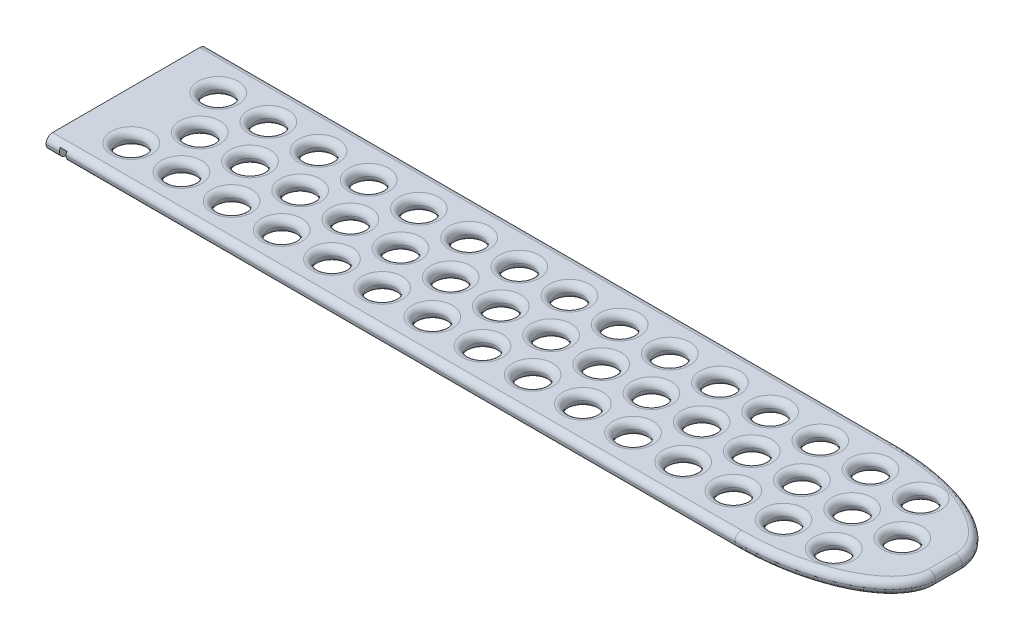
SolidWorks part; units mm, degrees
ref_plane "Front Plane" through (0, 0, 0) normal (0, 0, 1) x (1, 0, 0)
ref_plane "Top Plane" through (0, 0, 0) normal (0, 1, 0) x (1, 0, 0)
ref_plane "Right Plane" through (0, 0, 0) normal (1, 0, 0) x (0, 0, -1)
sketch "Sketch1" plane through (0, 0, 0) normal (0, 1, 0) x (1, 0, 0)
  line L1 (22.7264, 12) -> (146.7264, 12)
  line L2 (22.7264, 12) -> (22.7264, -12)
  line L3 (22.7264, -12) -> (146.7264, -12)
  line L4 (146.7264, 12) -> (146.7264, -12)
  dimension "D1" = 24
  dimension "D2" = 124
extrude "Boss-Extrude1" add sketch "Sketch1" along normal blind 2
fillet "Fillet1" radius 20 1 edges at (146.7264, 1, 12) second distance 10 first distance on face at (84.7264, 1, 12)
fillet "Fillet2" radius 20 1 edges at (146.7264, 1, -12) second distance 10 first distance on face at (84.7264, 1, -12)
sketch "Sketch4" plane through (0, 2, 0) normal (0, 1, 0) x (1, 0, 0)
  line L0 (30.9736, 6.5) -> (34.7264, 0) construction
  line L1 (34.7264, 0) -> (30.9736, -6.5) construction
  line L2 (22.7264, 12) -> (22.7264, -12) construction
  circle A0 centre (30.9736, 6.5) radius 2
  circle A1 centre (34.7264, 0) radius 2
  circle A2 centre (30.9736, -6.5) radius 2
  circle A3 centre (42.2292, 0) radius 2
  circle A4 centre (38.4764, 6.5) radius 2
  circle A5 centre (38.4764, -6.5) radius 2
  circle A6 centre (49.732, 0) radius 2
  circle A7 centre (45.9792, 6.5) radius 2
  circle A8 centre (45.9792, -6.5) radius 2
  circle A9 centre (57.2347, 0) radius 2
  circle A10 centre (53.482, 6.5) radius 2
  circle A11 centre (53.482, -6.5) radius 2
  circle A12 centre (64.7375, 0) radius 2
  circle A13 centre (60.9847, 6.5) radius 2
  circle A14 centre (60.9847, -6.5) radius 2
  circle A15 centre (72.2403, 0) radius 2
  circle A16 centre (68.4875, 6.5) radius 2
  circle A17 centre (68.4875, -6.5) radius 2
  circle A18 centre (79.7431, 0) radius 2
  circle A19 centre (75.9903, 6.5) radius 2
  circle A20 centre (75.9903, -6.5) radius 2
  circle A21 centre (87.2459, 0) radius 2
  circle A22 centre (83.4931, 6.5) radius 2
  circle A23 centre (83.4931, -6.5) radius 2
  circle A24 centre (94.7486, 0) radius 2
  circle A25 centre (90.9959, 6.5) radius 2
  circle A26 centre (90.9959, -6.5) radius 2
  circle A27 centre (102.2514, 0) radius 2
  circle A28 centre (98.4986, 6.5) radius 2
  circle A29 centre (98.4986, -6.5) radius 2
  circle A30 centre (109.7542, 0) radius 2
  circle A31 centre (106.0014, 6.5) radius 2
  circle A32 centre (106.0014, -6.5) radius 2
  circle A33 centre (117.257, 0) radius 2
  circle A34 centre (113.5042, 6.5) radius 2
  circle A35 centre (113.5042, -6.5) radius 2
  circle A36 centre (124.7597, 0) radius 2
  circle A37 centre (121.007, 6.5) radius 2
  circle A38 centre (121.007, -6.5) radius 2
  circle A39 centre (132.2625, 0) radius 2
  circle A40 centre (128.5097, 6.5) radius 2
  circle A41 centre (128.5097, -6.5) radius 2
  circle A42 centre (139.7653, 0) radius 2
  circle A43 centre (136.0125, 6.5) radius 2
  circle A44 centre (136.0125, -6.5) radius 2
  point P11 (22.7264, 0)
  dimension "D1" = 4
  dimension "D2" = 120
  dimension "D3" = 12
  dimension "D5" = 3.75
  dimension "D6" = 13
  dimension "D4" = 15
extrude "Cut-Extrude2" cut sketch "Sketch4" against normal through all
fillet "Fillet3" radius 1 102 edges at (30.9736, 0, -4.5) (113.5042, 0, 8.5) (117.257, 0, 2) (113.5042, 0, -4.5) (60.9847, 0, -4.5) (53.482, 0, 8.5) (57.2347, 0, 2) (53.482, 0, -4.5) (72.2403, 0, 2) (68.4875, 0, -4.5) (60.9847, 0, 8.5) (64.7375, 0, 2) (42.2292, 0, 2) (38.4764, 0, -4.5) (30.9736, 0, 8.5) (34.7264, 0, 2) (45.9792, 0, 8.5) (49.732, 0, 2) (45.9792, 0, -4.5) (38.4764, 0, 8.5) (102.2514, 0, 2) (98.4986, 0, -4.5) (90.9959, 0, 8.5) (94.7486, 0, 2) (106.0014, 0, 8.5) (109.7542, 0, 2) (106.0014, 0, -4.5) (98.4986, 0, 8.5) (75.9903, 0, 8.5) (79.7431, 0, 2) (75.9903, 0, -4.5) (68.4875, 0, 8.5) (90.9959, 0, -4.5) (83.4931, 0, 8.5) (87.2459, 0, 2) (83.4931, 0, -4.5) (30.9736, 2, -4.5) (113.5042, 2, 8.5) (117.257, 2, 2) (113.5042, 2, -4.5) (60.9847, 2, -4.5) (53.482, 2, 8.5) (57.2347, 2, 2) (53.482, 2, -4.5) (72.2403, 2, 2) (68.4875, 2, -4.5) (60.9847, 2, 8.5) (64.7375, 2, 2) (42.2292, 2, 2) (38.4764, 2, -4.5) (30.9736, 2, 8.5) (34.7264, 2, 2) (45.9792, 2, 8.5) (49.732, 2, 2) (45.9792, 2, -4.5) (38.4764, 2, 8.5) (102.2514, 2, 2) (98.4986, 2, -4.5) (90.9959, 2, 8.5) (94.7486, 2, 2) (106.0014, 2, 8.5) (109.7542, 2, 2) (106.0014, 2, -4.5) (98.4986, 2, 8.5) (75.9903, 2, 8.5) (79.7431, 2, 2) (75.9903, 2, -4.5) (68.4875, 2, 8.5) (90.9959, 2, -4.5) (83.4931, 2, 8.5) (87.2459, 2, 2) (83.4931, 2, -4.5) (124.7597, 0, 2) (121.007, 0, 8.5) (128.5097, 0, -4.5) (132.2625, 0, 2) (121.007, 0, -4.5) (136.0125, 0, 8.5) (139.7653, 0, 2) (136.0125, 0, -4.5) (128.5097, 0, 8.5) (124.7597, 2, 2) (121.007, 2, 8.5) (128.5097, 2, -4.5) (132.2625, 2, 2) (121.007, 2, -4.5) (136.0125, 2, 8.5) (139.7653, 2, 2) (136.0125, 2, -4.5) (128.5097, 2, 8.5) (22.7264, 0, 0) (22.7264, 2, 0)
sketch "Sketch11" plane through (0, 2, 0) normal (0, 1, 0) x (1, 0, 0)
  line L0 (126.7264, -12) -> (22.7264, -12) construction
  line L1 (22.7264, 12) -> (23.7264, 12)
  line L2 (22.7264, 12) -> (22.7264, -12)
  line L3 (22.7264, -12) -> (23.7264, -12)
  line L4 (23.7264, 12) -> (23.7264, -12)
  line L5 (23.7264, 11) -> (23.7264, -11) construction
extrude "Cut-Extrude6" cut sketch "Sketch11" against normal through all both and the other way through all
sketch "Sketch12" plane through (0, 0, 0) normal (0, -1, 0) x (1, 0, 0)
  line L0 (126.7264, 12) -> (23.7264, 12) construction
  line L1 (25.7264, 12) -> (26.7264, 12)
  line L2 (25.7264, 12) -> (25.7264, -12)
  line L3 (25.7264, -12) -> (26.7264, -12)
  line L4 (26.7264, 12) -> (26.7264, -12)
  line L5 (23.7264, -12) -> (126.7264, -12) construction
  line L6 (23.7264, 11) -> (23.7264, -11) construction
  dimension "D1" = 2
  dimension "D2" = 1
extrude "Cut-Extrude7" cut sketch "Sketch12" against normal blind 1.5
